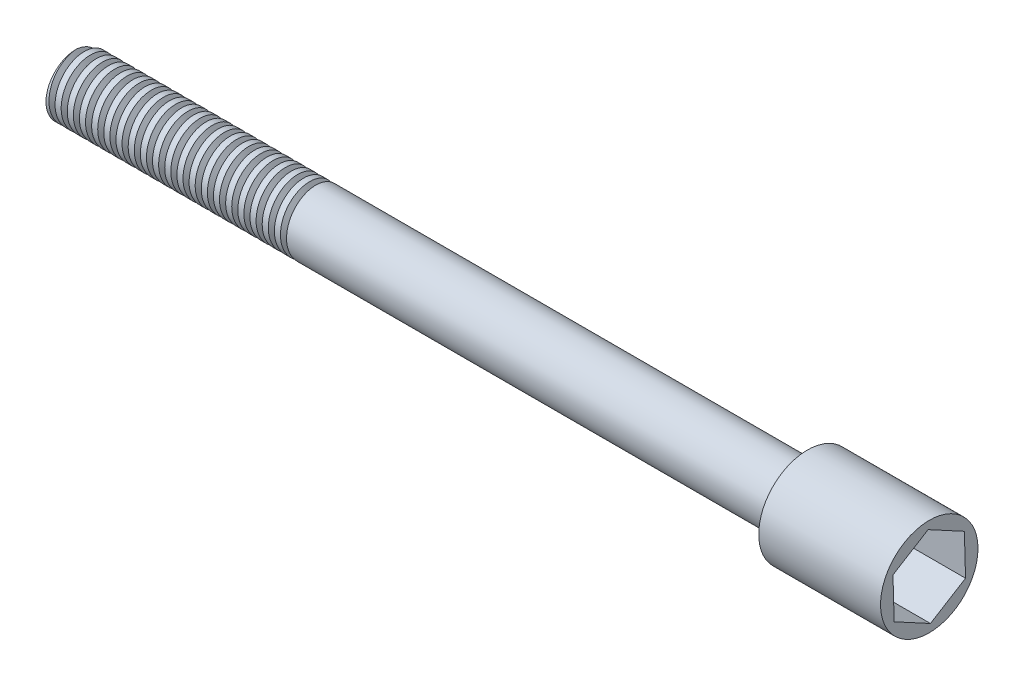
SolidWorks part; units mm, degrees
ref_plane "Front Plane" through (0, 0, 0) normal (0, 0, 1) x (1, 0, 0)
ref_plane "Top Plane" through (0, 0, 0) normal (0, 1, 0) x (1, 0, 0)
ref_plane "Right Plane" through (0, 0, 0) normal (1, 0, 0) x (0, 0, -1)
sketch "Sketch1" plane through (0, 0, 0) normal (0, 0, 1) x (1, 0, 0)
  line L0 (0, 0) -> (-70, 0)
  line L1 (-70, 0) -> (-70, 2.5)
  line L2 (-70, 2.5) -> (-10, 2.5)
  line L3 (-10, 2.5) -> (-10, 4)
  line L4 (-10, 4) -> (0, 4)
  line L5 (0, 4) -> (0, 0)
  dimension "D1" = 70
  dimension "D2" = 2.5
  dimension "D3" = 4
  dimension "D4" = 10
revolve "Revolve1" add sketch "Sketch1" angle 360 about L0
sketch "Sketch2" plane through (0, 0, 0) normal (1, 0, 0) x (0, 0, -1)
  line L1 (0.096, -3.3831) -> (2.9778, -1.6084)
  line L2 (2.9778, -1.6084) -> (2.8818, 1.7747)
  line L3 (2.8818, 1.7747) -> (-0.096, 3.3831)
  line L4 (-0.096, 3.3831) -> (-2.9778, 1.6084)
  line L5 (-2.9778, 1.6084) -> (-2.8818, -1.7747)
  line L6 (-2.8818, -1.7747) -> (0.096, -3.3831)
  circle A0 centre (0, 0) radius 2.931 construction
extrude "Cut-Extrude1" cut sketch "Sketch2" against normal blind 7
sketch "Sketch3" plane through (-70, 0, 0) normal (-1, 0, 0) x (0, 0, 1)
  circle A1 centre (0, 0) radius 2.5
curve "Helix/Spiral1" pitch 1 height 20 radius 2.5 centre (-70, 0, 0) axis (1, 0, 0) start towards (0, 0, -1)
sketch "Sketch9" plane through (0, 0, 0) normal (0, 1, 0) x (1, 0, 0)
  line L1 (-70, 2.0659) -> (-69.624, 2.7171)
  line L2 (-69.624, 2.7171) -> (-70.376, 2.7171)
  line L3 (-70.376, 2.7171) -> (-70, 2.0659)
  circle A0 centre (-70, 2.5) radius 0.2171 construction
sweep "Cut-Sweep1" cut profiles "Sketch9" path "Helix/Spiral1" align with end faces yes
